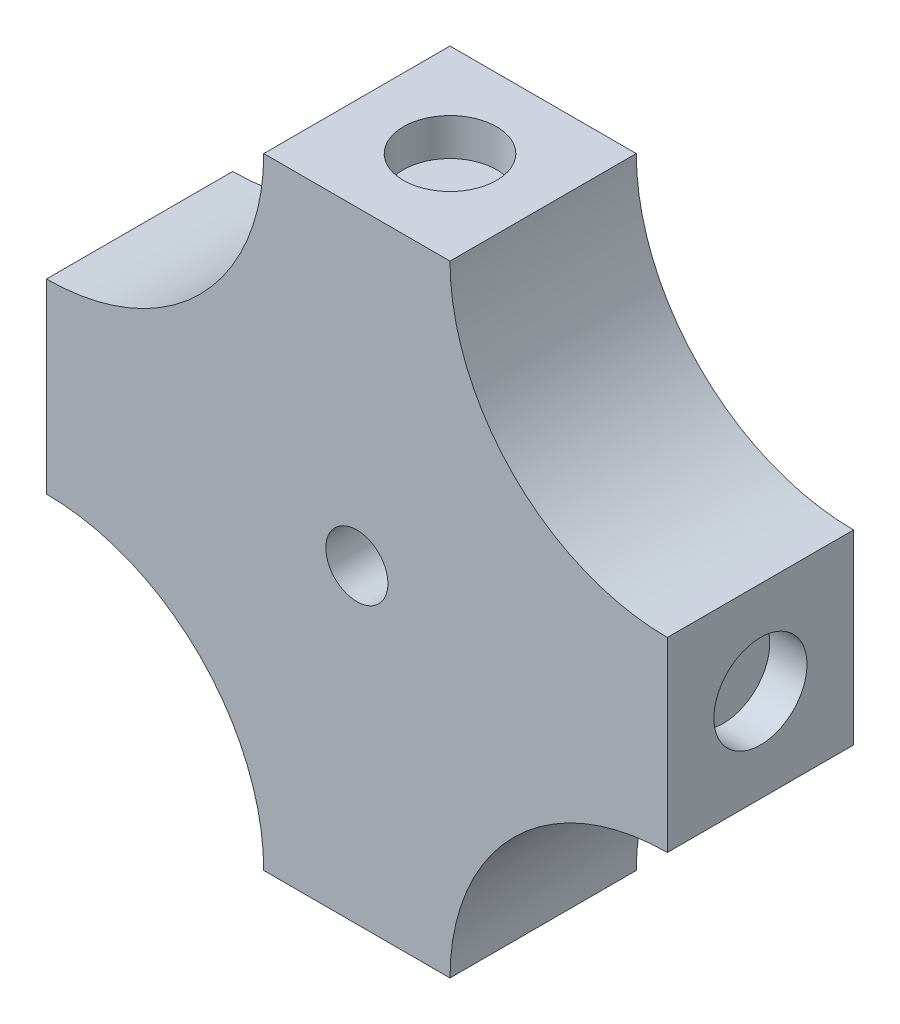
SolidWorks part; units mm, degrees
ref_plane "Front Plane" through (0, 0, 0) normal (0, 0, 1) x (1, 0, 0)
ref_plane "Top Plane" through (0, 0, 0) normal (0, 1, 0) x (1, 0, 0)
ref_plane "Right Plane" through (0, 0, 0) normal (1, 0, 0) x (0, 0, -1)
sketch "Sketch10" plane through (0, 0, 0) normal (0, 0, 1) x (1, 0, 0)
  line L1 (-268.8684, 145.0883) -> (-262.8684, 145.0883)
  line L2 (-268.8684, 145.0883) -> (-268.8684, 125.0883)
  line L3 (-268.8684, 125.0883) -> (-262.8684, 125.0883)
  line L4 (-262.8684, 145.0883) -> (-262.8684, 125.0883)
  line L5 (-275.8684, 138.0883) -> (-255.8684, 138.0883)
  line L6 (-275.8684, 138.0883) -> (-275.8684, 132.0883)
  line L7 (-275.8684, 132.0883) -> (-255.8684, 132.0883)
  line L8 (-255.8684, 138.0883) -> (-255.8684, 132.0883)
  dimension "D1" = 20
  dimension "D2" = 20
  dimension "D3" = 6
  dimension "D4" = 6
  dimension "D5" = 7
  dimension "D6" = 7
extrude "Boss-Extrude4" add sketch "Sketch10" along normal blind 6 contours L6 L7 L2 L5 | L7 L2 L3 L4 | L8 L5 L4 L7 | L2 L7 L4 L5 | L2 L5 L4 L1 region at (-265.8684, 141.5883, 0) region at (-265.8684, 135.0883, 0) region at (-272.3684, 135.0883, 0) region at (-259.3684, 135.0883, 0) region at (-265.8684, 128.5883, 0)
sketch "Sketch11" plane through (0, 145.0883, 0) normal (0, 1, 0) x (1, 0, 0)
  line L0 (-268.8684, 0) -> (-262.8684, 0) construction
  line L1 (-268.8684, -6) -> (-268.8684, 0) construction
  circle A0 centre (-265.8684, -3) radius 1.5
  dimension "D1" = 3
  dimension "D2" = 3
  dimension "D3" = 3
extrude "Cut-Extrude3" cut sketch "Sketch11" against normal blind 1.2
sketch "Sketch14" plane through (-275.8684, 0, 0) normal (-1, 0, 0) x (0, 0, 1)
  line L0 (6, 138.0883) -> (6, 132.0883) construction
  line L1 (6, 138.0883) -> (0, 138.0883) construction
  circle A0 centre (3, 135.0883) radius 1.5
  point P6 (3, 138.0883)
  dimension "D1" = 3
  dimension "D2" = 3
  dimension "D3" = 3
extrude "Cut-Extrude4" cut sketch "Sketch14" against normal blind 1.2
sketch "Sketch15" plane through (0, 125.0883, 0) normal (0, -1, 0) x (-1, 0, 0)
  line L0 (268.8684, -6) -> (268.8684, 0) construction
  line L1 (268.8684, -6) -> (262.8684, -6) construction
  circle A0 centre (265.8684, -3) radius 1.5
  dimension "D1" = 3
  dimension "D2" = 3
  dimension "D3" = 3
extrude "Cut-Extrude5" cut sketch "Sketch15" against normal blind 1.2
sketch "Sketch16" plane through (-255.8684, 0, 0) normal (1, 0, 0) x (0, 0, -1)
  line L0 (0, 138.0883) -> (0, 132.0883) construction
  line L1 (-6, 132.0883) -> (0, 132.0883) construction
  circle A0 centre (-3, 135.0883) radius 1.5
  dimension "D1" = 3
  dimension "D2" = 3
  dimension "D3" = 3
extrude "Cut-Extrude7" cut sketch "Sketch16" against normal blind 1.2
fillet "Fillet1" radius 7 1 edges at (-262.8684, 138.0883, 3) type face fillet first side face at (-262.8684, 141.5883, 3) second side face at (-259.3684, 138.0883, 3)
fillet "Fillet2" radius 7 1 edges at (-268.8684, 138.0883, 3) type face fillet first side face at (-272.3684, 138.0883, 3) second side face at (-268.8684, 141.5883, 3)
fillet "Fillet3" radius 7 1 edges at (-268.8684, 132.0883, 3) type face fillet first side face at (-268.8684, 128.5883, 3) second side face at (-272.3684, 132.0883, 3)
fillet "Fillet4" radius 7 1 edges at (-262.8684, 132.0883, 3) type face fillet first side face at (-259.3684, 132.0883, 3) second side face at (-262.8684, 128.5883, 3)
sketch "Sketch17" plane through (0, 0, 0) normal (0, 0, -1) x (-1, 0, 0)
  line L0 (268.8684, 145.0883) -> (262.8684, 145.0883) construction
  line L1 (255.8684, 138.0883) -> (255.8684, 132.0883) construction
  circle A0 centre (265.8684, 135.0883) radius 1
  dimension "D1" = 2
  dimension "D2" = 10
  dimension "D3" = 10
extrude "Cut-Extrude8" cut sketch "Sketch17" against normal blind 6
